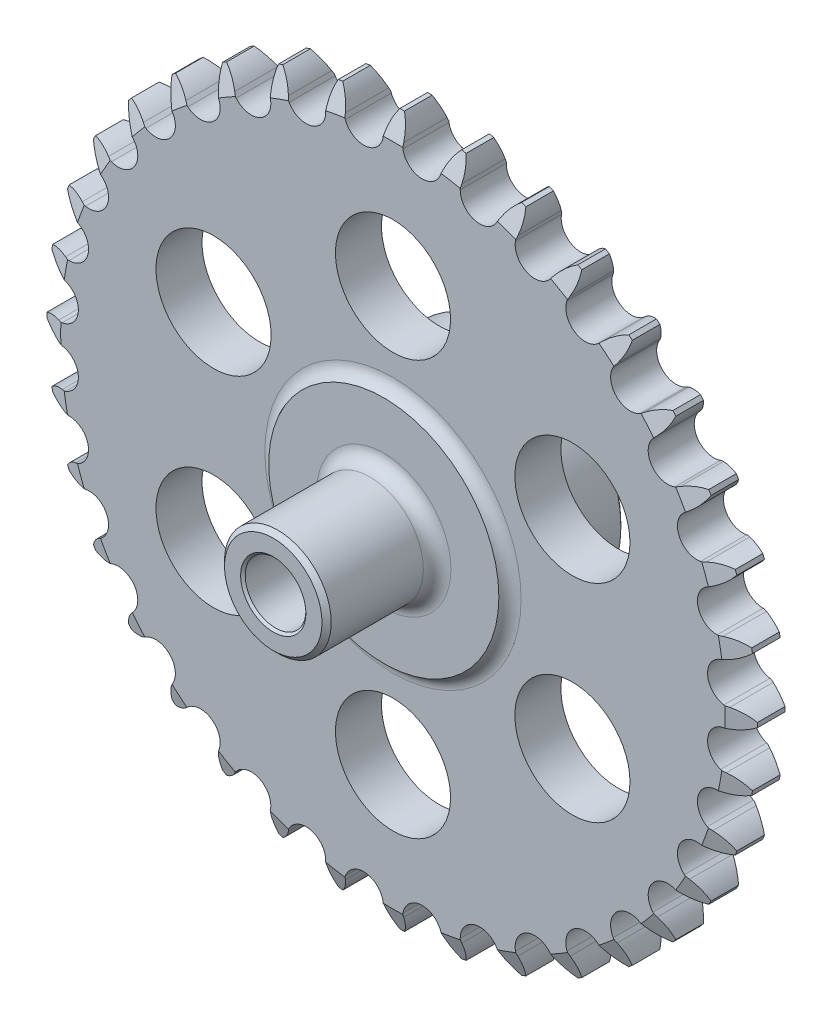
SolidWorks part; units mm, degrees
material "AISI 316 Annealed Stainless Steel Bar (SS)"
ref_plane "Front Plane" through (0, 0, 0) normal (0, 0, 1) x (1, 0, 0)
ref_plane "Top Plane" through (0, 0, 0) normal (0, 1, 0) x (1, 0, 0)
ref_plane "Right Plane" through (0, 0, 0) normal (1, 0, 0) x (0, 0, -1)
ref_axis "Axis1" through (0, 0, -22.55) along (0, 0, 1)
sketch "Sketch1" plane through (0, 0, 0) normal (0, 0, 1) x (1, 0, 0)
  line L0 (0, 0) -> (0, 72.8581) construction
  line L1 (-2.1568, 71.8581) -> (2.1568, 71.8581) construction
  line L2 (-2.1568, 71.8581) -> (-2.0429, 72.8581) construction
  line L3 (2.1568, 71.8581) -> (2.0429, 72.8581) construction
  line L4 (-2.0429, 72.8581) -> (2.0429, 72.8581) construction
  line L7 (-0.5, 77.163) -> (0.5, 77.163) construction
  circle A0 centre (0, 0) radius 72.8581 construction
  circle A1 centre (6.35, 72.5808) radius 4.255 construction
  circle A2 centre (-6.35, 72.5808) radius 4.255 construction
  circle A3 centre (0, 0) radius 68.6031 construction
  arc A4 (-2.0429, 72.8581) -> (-0.5, 77.163) centre (7.8928, 71.726) cw construction
  arc A5 (2.0429, 72.8581) -> (0.5, 77.163) centre (-7.8928, 71.726) ccw construction
  dimension "D1" = 13
  dimension "SprocketPitchDiameter" = 145.7162
  dimension "RollerDia" = 8.51
  dimension "D4" = 10
  dimension "ChainPitch" = 12.7
  dimension "D2" = 1
  dimension "D3" = 1
  dimension "D5" = 1
sketch "Sketch2" plane through (0, 0, 0) normal (0, 0, 1) x (1, 0, 0)
  circle A0 centre (0, 0) radius 68.6031 construction
  circle A1 centre (0, 0) radius 68.6031
extrude "Boss-Extrude1" add sketch "Sketch2" along normal mid plane 10
sketch "Sketch4" plane through (0, 0, 0) normal (0, 0, 1) x (1, 0, 0)
  line L0 (-0.5, 77.163) -> (0.5, 77.163) construction
  line L1 (-2.1568, 71.8581) -> (-2.0429, 72.8581) construction
  line L2 (2.1568, 71.8581) -> (2.0429, 72.8581) construction
  line L3 (-0.5, 77.163) -> (0.5, 77.163)
  line L4 (-2.1568, 71.8581) -> (-2.0429, 72.8581)
  line L5 (2.1568, 71.8581) -> (2.0429, 72.8581)
  circle A0 centre (0, 0) radius 68.6031 construction
  circle A1 centre (6.35, 72.5808) radius 4.255 construction
  circle A2 centre (-6.35, 72.5808) radius 4.255 construction
  arc A3 (2.0429, 72.8581) -> (0.5, 77.163) centre (-7.8928, 71.726) ccw construction
  arc A4 (-0.5, 77.163) -> (-2.0429, 72.8581) centre (7.8928, 71.726) ccw construction
  arc A5 (5.9792, 68.342) -> (-5.9792, 68.342) centre (0, 0) ccw
  arc A6 (2.1568, 71.8581) -> (5.9792, 68.342) centre (6.35, 72.5808) ccw
  arc A7 (-5.9792, 68.342) -> (-2.1568, 71.8581) centre (-6.35, 72.5808) ccw
  arc A8 (2.0429, 72.8581) -> (0.5, 77.163) centre (-7.8928, 71.726) ccw
  arc A9 (-0.5, 77.163) -> (-2.0429, 72.8581) centre (7.8928, 71.726) ccw
extrude "Boss-Extrude2" add sketch "Sketch4" along normal up to surface and the other way up to surface up to face at (68.6031, 0, 5) other way up to face at (68.6031, 0, -5)
pattern_circular "CirPattern1" count 36 over 360 about axis through (0, 0, 5) along (0, 0, -1) of "Boss-Extrude2"
sketch "Sketch5" plane through (0, 0, 0) normal (1, 0, 0) x (0, 0, -1)
  line L0 (0, 0) -> (-6, 0) construction
  line L1 (0, 77.163) -> (0, 72.8581) construction
  line L2 (-6, 84.663) -> (6, 84.663)
  line L3 (-6, 84.663) -> (-6, 69.663)
  line L4 (-6, 69.663) -> (6, 69.663) construction
  line L5 (6, 84.663) -> (6, 69.663)
  line L6 (-6, 84.663) -> (6, 69.663) construction
  line L7 (-6, 69.663) -> (6, 84.663) construction
  line L8 (-6, 69.663) -> (0, 84.663)
  line L9 (6, 69.663) -> (0, 84.663)
  line L10 (0, 77.163) -> (0, 72.8581) construction
  point P1 (0, 77.163)
  dimension "D1" = 15
  dimension "D2" = 1
revolve "Cut-Revolve7" cut sketch "Sketch5" angle 360 about L0 region at (0, 79.663, -4) region at (0, 79.663, 4)
sketch "Sketch6" plane through (0, 0, 0) normal (0, 0, 1) x (1, 0, 0)
  circle A0 centre (0, 0) radius 25
  dimension "D1" = 50
extrude "Boss-Extrude3" add sketch "Sketch6" along normal blind 7 and the other way blind 20
sketch "Sketch7" plane through (0, 0, 0) normal (0, 0, 1) x (1, 0, 0)
  circle A0 centre (0, 0) radius 6.586
  dimension "D1" = 13.1719
extrude "Cut-Extrude1" cut sketch "Sketch7" against normal through all both and the other way through all
sketch "Sketch9" plane through (0, 0, 7) normal (0, 0, 1) x (1, 0, 0)
  circle A2 centre (0, 0) radius 11.586
  circle A3 centre (0, 0) radius 11.586
  circle M2 centre (0, 0) radius 6.586
  dimension "D1" = 5
extrude "Boss-Extrude4" add sketch "Sketch9" along normal blind 24 contours A3 M2 region at (-11.2583, 0, 7)
fillet "Fillet1" radius 3 2 edges at (11.586, 0, 7) (25, 0, 5)
chamfer "Chamfer1" distance 1 angle 45 1 edges at (11.586, 0, 31)
chamfer "Chamfer2" distance 0.5 angle 45 3 edges at (6.586, 0, 31) (25, 0, -20) (6.586, 0, -20)
fillet "Fillet2" radius 0.5 1 edges at (25, 0, -5)
sketch "Sketch8" plane through (0, 0, 0) normal (0, 0, 1) x (1, 0, 0)
  circle A0 centre (0, 45) radius 12.5
  dimension "D2" = 25
  dimension "D1" = 45
extrude "Cut-Extrude2" cut sketch "Sketch8" against normal through all both and the other way through all
pattern_circular "CirPattern2" count 6 over 360 about axis through (0, 0, 6) along (0, 0, 1) of "Cut-Extrude2"
equation "\"ChainPitch\"=12.7"
equation "\"ChainPitch@Sketch1\"=\"ChainPitch\""
equation "\"SprocketPitchDiameter@Sketch1\" = \"ChainPitch\" / sin ( 180 / \"NumberOfTeeth\" )"
equation "\"NumberOfTeeth\"= 36"
equation "\"D1@CirPattern1\"=\"NumberOfTeeth\""
